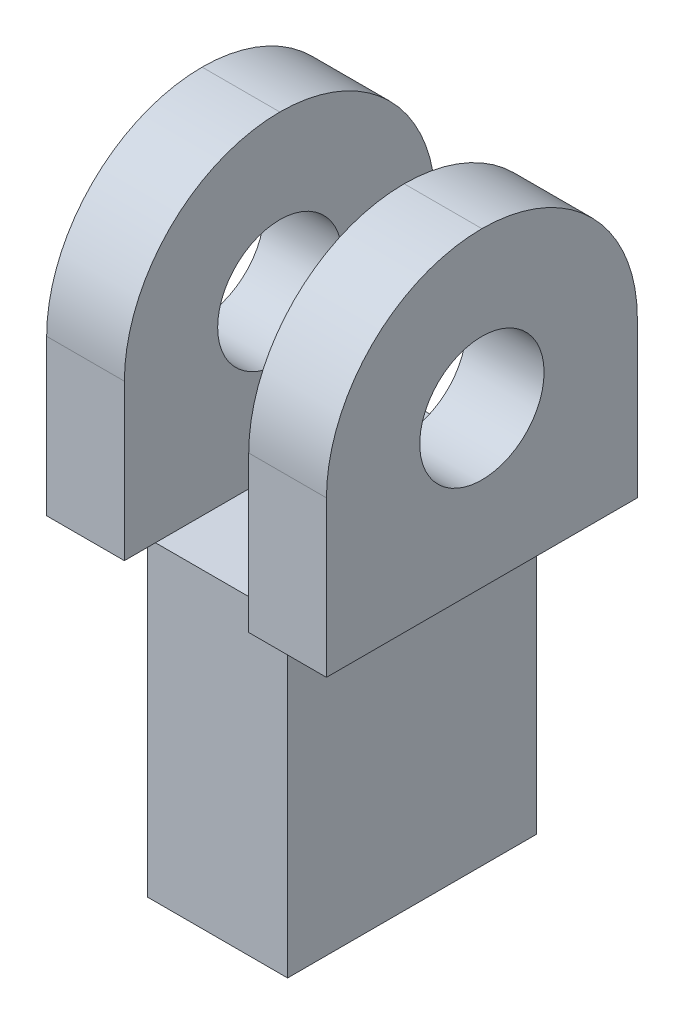
SolidWorks part; units mm, degrees
ref_plane "Front Plane" through (0, 0, 0) normal (0, 0, 1) x (1, 0, 0)
ref_plane "Top Plane" through (0, 0, 0) normal (0, 1, 0) x (1, 0, 0)
ref_plane "Right Plane" through (0, 0, 0) normal (1, 0, 0) x (0, 0, -1)
sketch "Sketch1" plane through (0, 0, 0) normal (0, 1, 0) x (1, 0, 0)
  line L1 (-4.5, -8) -> (4.5, -8)
  line L2 (-4.5, -8) -> (-4.5, 8)
  line L3 (-4.5, 8) -> (4.5, 8)
  line L4 (4.5, -8) -> (4.5, 8)
  line L5 (-4.5, -8) -> (4.5, 8) construction
  line L6 (-4.5, 8) -> (4.5, -8) construction
  point P0 (0, 0)
  dimension "D1" = 9
  dimension "D2" = 16
extrude "Boss-Extrude1" add sketch "Sketch1" along normal blind 20
sketch "Sketch2" plane through (0, 0, 0) normal (0, -1, 0) x (1, 0, 0)
  line L1 (-4.1, -7.6) -> (4.1, -7.6)
  line L2 (-4.1, -7.6) -> (-4.1, 7.6)
  line L3 (-4.1, 7.6) -> (4.1, 7.6)
  line L4 (4.1, -7.6) -> (4.1, 7.6)
  line L5 (-4.1, -7.6) -> (4.1, 7.6) construction
  line L6 (-4.1, 7.6) -> (4.1, -7.6) construction
  point P0 (0, 0)
  dimension "D1" = 8.2
  dimension "D2" = 15.2
extrude "Cut-Extrude1" cut sketch "Sketch2" against normal blind 18
sketch "Sketch4" plane through (0, 20, 0) normal (0, 1, 0) x (1, 0, 0)
  line L5 (4, 10) -> (9, 10)
  line L6 (4, 10) -> (4, -10)
  line L7 (4, -10) -> (9, -10)
  line L8 (9, 10) -> (9, -10)
  line L9 (4, 10) -> (9, -10) construction
  line L10 (4, -10) -> (9, 10) construction
  line L11 (-9, 10) -> (-4, 10)
  line L12 (-9, 10) -> (-9, -10)
  line L13 (-9, -10) -> (-4, -10)
  line L14 (-4, 10) -> (-4, -10)
  line L15 (-9, 10) -> (-4, -10) construction
  line L16 (-9, -10) -> (-4, 10) construction
  point P0 (6.5, 0)
  point P6 (-6.5, 0)
  dimension "D1" = 5
  dimension "D2" = 4
  dimension "D3" = 4
  dimension "D4" = 20
extrude "Boss-Extrude2" add sketch "Sketch4" along normal blind 20
sketch "Sketch5" plane through (9, 0, 0) normal (1, 0, 0) x (0, 0, -1)
  line L0 (10, 40) -> (-10, 40) construction
  circle A0 centre (0, 30) radius 4
  dimension "D2" = 8
  dimension "D1" = 10
extrude "Cut-Extrude2" cut sketch "Sketch5" against normal through all
fillet "Fillet1" radius 10 4 edges at (6.5, 40, 10) (6.5, 40, -10) (-6.5, 40, -10) (-6.5, 40, 10)
equation "\"D3@Sketch4\"=\"D2@Sketch4\""
